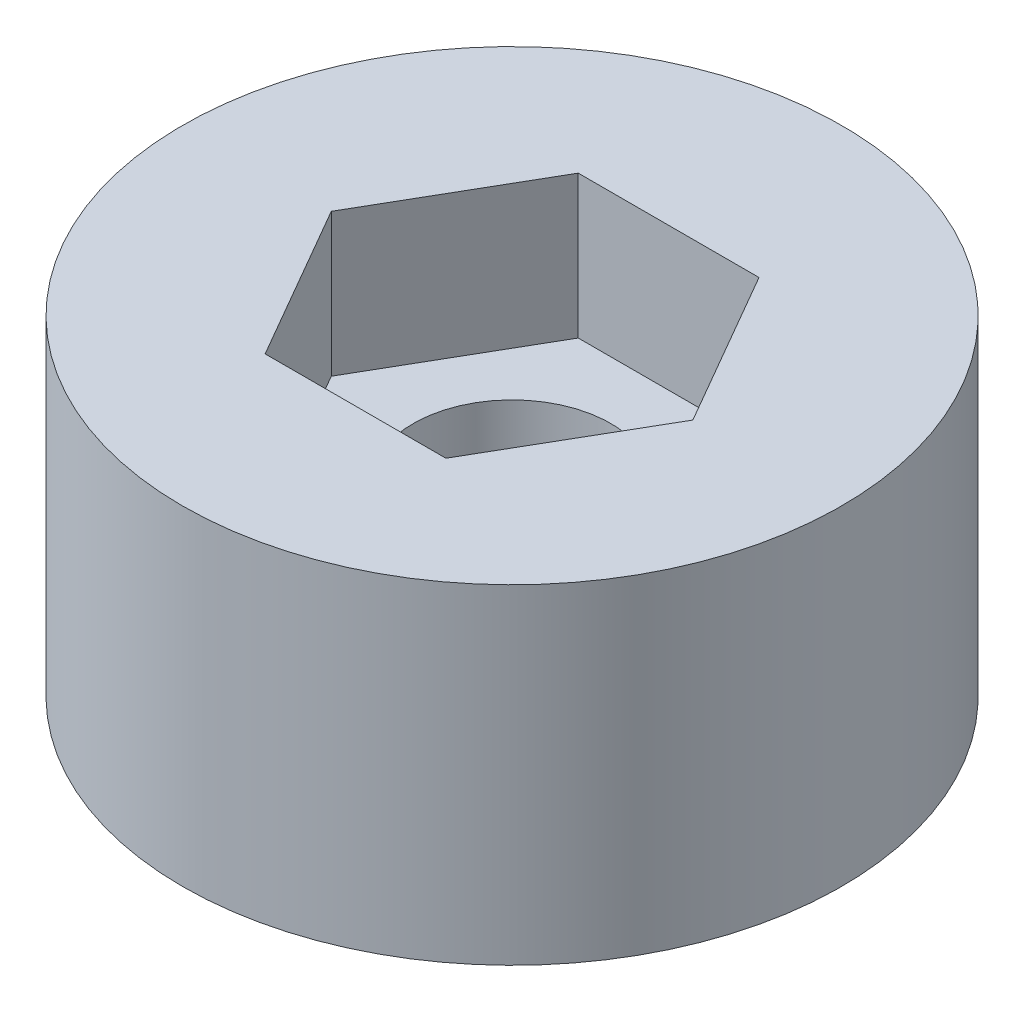
SolidWorks part; units mm, degrees
ref_plane "Front Plane" through (0, 0, 0) normal (0, 0, 1) x (1, 0, 0)
ref_plane "Top Plane" through (0, 0, 0) normal (0, 1, 0) x (1, 0, 0)
ref_plane "Right Plane" through (0, 0, 0) normal (1, 0, 0) x (0, 0, -1)
sketch "Sketch1" plane through (0, 0, 0) normal (0, 1, 0) x (1, 0, 0)
  circle A0 centre (0, 0) radius 6
  dimension "D1" = 12
extrude "Boss-Extrude1" add sketch "Sketch1" along normal blind 6
sketch "Sketch2" plane through (0, 6, 0) normal (0, 1, 0) x (1, 0, 0)
  line L1 (3.2909, 0) -> (1.6454, 2.85)
  line L2 (1.6454, 2.85) -> (-1.6454, 2.85)
  line L3 (-1.6454, 2.85) -> (-3.2909, 0)
  line L4 (-3.2909, 0) -> (-1.6454, -2.85)
  line L5 (-1.6454, -2.85) -> (1.6454, -2.85)
  line L6 (1.6454, -2.85) -> (3.2909, 0)
  circle A0 centre (0, 0) radius 1.8
  circle A1 centre (0, 0) radius 2.85 construction
  dimension "D1" = 3.6
  dimension "D2" = 5.7
extrude "Cut-Extrude1" cut sketch "Sketch2" against normal blind 2.6
extrude "Cut-Extrude2" cut sketch "Sketch2<2>" against normal through all contours A0 region at (0, 6, 0)
sketch "Sketch2<2>" plane through (0, 6, 0) normal (0, 1, 0) x (1, 0, 0) same geometry as "Sketch2"
sketch "Sketch3" plane through (0, 0, 0) normal (0, -1, 0) x (1, 0, 0)
  line L0 (0, 1.8) -> (0, 2.8)
  line L1 (0, -2.8) -> (0, -1.8)
  arc A0 (0, 1.8) -> (0, -1.8) centre (0, 0) ccw
  circle A1 centre (0, 0) radius 1.8 construction
  arc A2 (0, 2.8) -> (0, -2.8) centre (0, 0) ccw
  dimension "D1" = 1
extrude "Boss-Extrude2" add sketch "Sketch3" along normal blind 2.5
sketch "Sketch4" plane through (0, -2.5, 0) normal (0, -1, 0) x (1, 0, 0)
  line L1 (-6, -1.45) -> (-1.8, -1.45)
  line L2 (-6, -1.45) -> (-6, 1.45)
  line L3 (-6, 1.45) -> (-1.8, 1.45)
  line L4 (-1.8, -1.45) -> (-1.8, 1.45)
  line L5 (-6, -1.45) -> (-1.8, 1.45) construction
  line L6 (-6, 1.45) -> (-1.8, -1.45) construction
  arc A0 (0, 1.8) -> (0, -1.8) centre (0, 0) ccw construction
  point P0 (-3.9, 0)
  dimension "D1" = 6
  dimension "D2" = 2.9
extrude "Boss-Extrude3" add sketch "Sketch4" against normal blind 1.2
fillet "Fillet4" radius 1 1 edges at (-6, -1.3, 0)
fillet "Fillet2" radius 0.5 9 edges at (-2.3953, -1.9, 1.45) (-2.3953, -1.9, -1.45) (-2.8, -1.3, 0) (-6, -2.4, 1.45) (-6, -2.4, -1.45) (-3.6977, -1.3, 1.45) (-5.7071, -1.5929, 1.45) (-3.6977, -1.3, -1.45) (-5.7071, -1.5929, -1.45)
fillet "Fillet3" radius 0.5 1 edges at (-2.8, 0, 0)
fillet "Fillet5" radius 1.8 2 edges at (0, 0, 2.55) (0, 0, -2.55)
